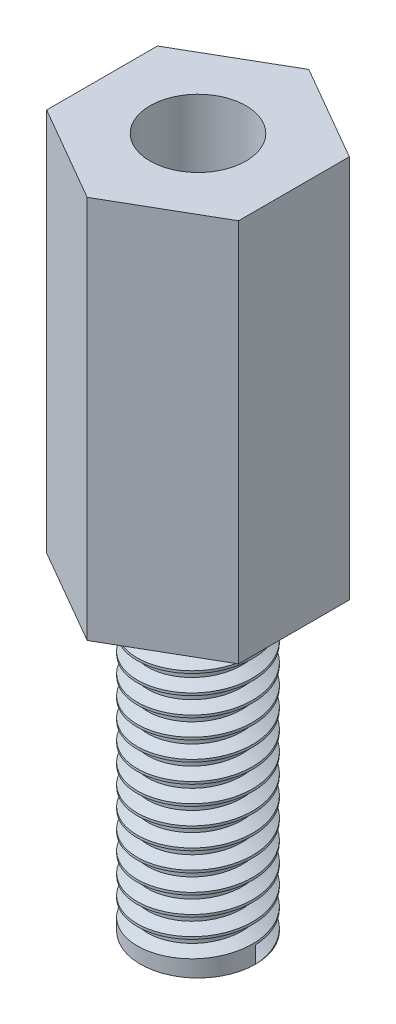
SolidWorks part; units mm, degrees
material "6061-T6 (SS)"
ref_plane "Front" through (0, 0, 0) normal (0, 0, 1) x (1, 0, 0)
ref_plane "Top" through (0, 0, 0) normal (0, 1, 0) x (1, 0, 0)
ref_plane "Right" through (0, 0, 0) normal (1, 0, 0) x (0, 0, -1)
sketch "Sketch1" plane through (0, 0, 0) normal (0, 0, 1) x (1, 0, 0)
  line L0 (0, 0) -> (0, 18)
  line L1 (0, 18) -> (5, 18)
  line L2 (5, 18) -> (5, 8)
  line L3 (5, 8) -> (1.5, 8)
  line L4 (1.5, 8) -> (1.5, 0)
  line L5 (1.5, 0) -> (0, 0)
  point P3 (0.75, 0)
  dimension "D1" = 1.5
  dimension "D2" = 5
  dimension "D3" = 10
  dimension "D4" = 8
revolve "Revolve1" add sketch "Sketch1" angle 360 about L0
sketch "Sketch2" plane through (0, 0, 0) normal (0, 1, 0) x (1, 0, 0)
  line L0 (0, -2.8868) -> (-2.5, -1.4434)
  line L1 (-2.5, -1.4434) -> (-2.5, 1.4434)
  line L2 (-2.5, 1.4434) -> (0, 2.8868)
  line L3 (0, 2.8868) -> (2.5, 1.4434)
  line L4 (2.5, 1.4434) -> (2.5, -1.4434)
  line L5 (2.5, -1.4434) -> (0, -2.8868)
  line L6 (0, 2.8868) -> (0, -2.8868) construction
  point P2 (0, 0)
  dimension "D1" = 120
  dimension "D2" = 5
  dimension "D3" = 60
extrude "Cut-Extrude2" cut sketch "Sketch2" against normal through all and the other way through all flip side to cut
thread "Thread1" pitch 0.5 method cut profile "Thread Profile1" start angle 0, offset 0, length 0, pitch 0.5, diameter 3
ref_plane "Plane1" through (1.5, 0, 0) normal (0, 0, 1) x (1, 0, 0)
sketch "Thread Profile1" plane through (1.5, 0, 0) normal (0, 0, 1) x (1, 0, 0)
  line L0 (0, 0) -> (0, 0.5) construction
  line L11 (0, 0) -> (0, 0.4375)
  line L12 (0, 0.4375) -> (-0.2706, 0.2812)
  line L13 (-0.2706, 0.2812) -> (-0.2706, 0.1562)
  line L15 (-0.2706, 0.1562) -> (0, 0)
  line L17 (-0.2706, 0.2187) -> (0, 0.2187) construction
  point P2 (0, 0)
  dimension "Pitch" = 0.5
  dimension "Profile_Angle" = 60
  dimension "Profile_Land" = 0.125
  dimension "Profile_Height" = 0.2706
hole_wizard "M3 Tapped Hole1" positions "Sketch7" profile "Sketch8" tap size "M3" standard "DIN"
sketch "Sketch7" plane through (0, 18, 18) normal (0, 1, 0) x (1, 0, 0)
  point P1 (0, 18)
sketch "Sketch8" plane through (0, 18, 0) normal (1, 0, 0) x (0, 0, 1)
  line L0 (0, 0) -> (0, 10.2511)
  line L1 (0, 10.2511) -> (1.25, 9.5)
  line L2 (1.25, 9.5) -> (1.25, 0)
  line L5 (1.25, 0) -> (0, 0)
  line L10 (0, 10.2511) -> (-1.25, 9.5) construction
  line L11 (0, -6.35) -> (0, 107.95) construction
  dimension "Tap Drill Dia." = 2.5
  dimension "Tap Drill Depth" = 9.5
  dimension "Drill Angle" = 118
cosmetic thread "Hole Thread3" parameters "D1"=8, "D2"=3
